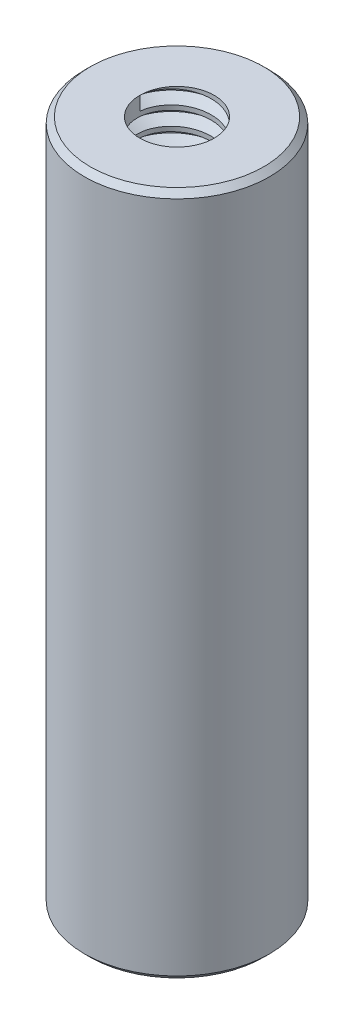
SolidWorks part; units mm, degrees
material "6061-T6 (SS)"
ref_plane "Alzado" through (0, 0, 0) normal (0, 0, 1) x (1, 0, 0)
ref_plane "Planta" through (0, 0, 0) normal (0, 1, 0) x (1, 0, 0)
ref_plane "Vista lateral" through (0, 0, 0) normal (1, 0, 0) x (0, 0, -1)
sketch "Croquis2" plane through (0, 0, 0) normal (0, 1, 0) x (1, 0, 0)
  circle A0 centre (0, 0) radius 6.35
  dimension "D1" = 12.7
extrude "Saliente-Extruir1" add sketch "Croquis2" along normal mid plane 46.99
chamfer "Chaflán1" distance 0.3969 angle 45 2 edges at (0, -23.495, 6.35) (0, 23.495, 6.35)
sketch "Croquis3" plane through (0, 0, 0) normal (0, 1, 0) x (1, 0, 0)
  circle A0 centre (0, 0) radius 2.5527
  dimension "D1" = 5.1054
extrude "Tap Hole 1" cut sketch "Croquis3" against normal blind 19.05 from surface starting at face at (0, 23.495, 5.9531)
extrude "Tap Hole 2" cut sketch "Croquis3<2>" along normal blind 19.05 from surface starting at face at (0, -23.495, 5.9531)
sketch "Croquis3<2>" plane through (0, 0, 0) normal (0, 1, 0) x (1, 0, 0) same geometry as "Croquis3"
sketch "Croquis4" plane through (0, 0, 0) normal (0, 1, 0) x (1, 0, 0)
  circle A0 centre (0, 0) radius 3.2639
  dimension "D1" = 6.5278
extrude "Clearance Hole" [suppressed] cut sketch "Croquis4" against normal through all both and the other way through all
thread "Rosca1" pitch 1.27 method cut profile "Perfil de rosca1" start angle 0, offset 0, length 0, pitch 1.27, diameter 5.1054
ref_plane "Plano1" through (-2.5527, 23.495, 0) normal (0, 0, 1) x (-1, 0, 0)
sketch "Perfil de rosca1" plane through (-2.5527, 23.495, 0) normal (0, 0, 1) x (-1, 0, 0)
  line L0 (0, 0) -> (0, 1.27) construction
  line L1 (0, 0) -> (0.6874, 0.3969)
  line L2 (0.6874, 0.3969) -> (0.6874, 0.5556)
  line L3 (0.6874, 0.5556) -> (0, 0.9525)
  line L4 (0.6874, 0.4762) -> (0, 0.4762) construction
  line L11 (0, 0) -> (0, 0.9525)
  point P2 (0, 0)
  dimension "Pitch" = 1.27
  dimension "Profile_Angle" = 60
  dimension "Profile_Land" = 0.1588
  dimension "Profile_Height" = 0.6874
thread "Rosca2" pitch 1.27 method cut profile "Perfil de rosca2" start angle 0, offset 0, length 0, pitch 1.27, diameter 5.1054
ref_plane "Plano2" through (2.5527, -23.495, 0) normal (0, 0, 1) x (1, 0, 0)
sketch "Perfil de rosca2" plane through (2.5527, -23.495, 0) normal (0, 0, 1) x (1, 0, 0)
  line L0 (0, 0) -> (0, 1.27) construction
  line L1 (0, 0) -> (0.6874, 0.3969)
  line L2 (0.6874, 0.3969) -> (0.6874, 0.5556)
  line L3 (0.6874, 0.5556) -> (0, 0.9525)
  line L4 (0.6874, 0.4762) -> (0, 0.4762) construction
  line L11 (0, 0) -> (0, 0.9525)
  point P2 (0, 0)
  dimension "Pitch" = 1.27
  dimension "Profile_Angle" = 60
  dimension "Profile_Land" = 0.1588
  dimension "Profile_Height" = 0.6874
equation "\"OD\"= 0.5pulgadas"
equation "\"Largo\"=1.85"
equation "\"Tap Hole\"= IIF ( \"OD\" = 0.375pulgadas , 0.1590pulgadas , 0.201pulgadas )"
equation "\"Spacer Hole\"= IIF ( \"OD\" = 0.375pulgadas , 0.196pulgadas , 0.257pulgadas )"
equation "\"D1@Croquis2\"=\"OD\""
equation "\"D1@Saliente-Extruir1\"=\"Largo\""
equation "\"D1@Croquis3\"=\"Tap Hole\""
equation "\"D1@Croquis4\"=\"Spacer Hole\""
